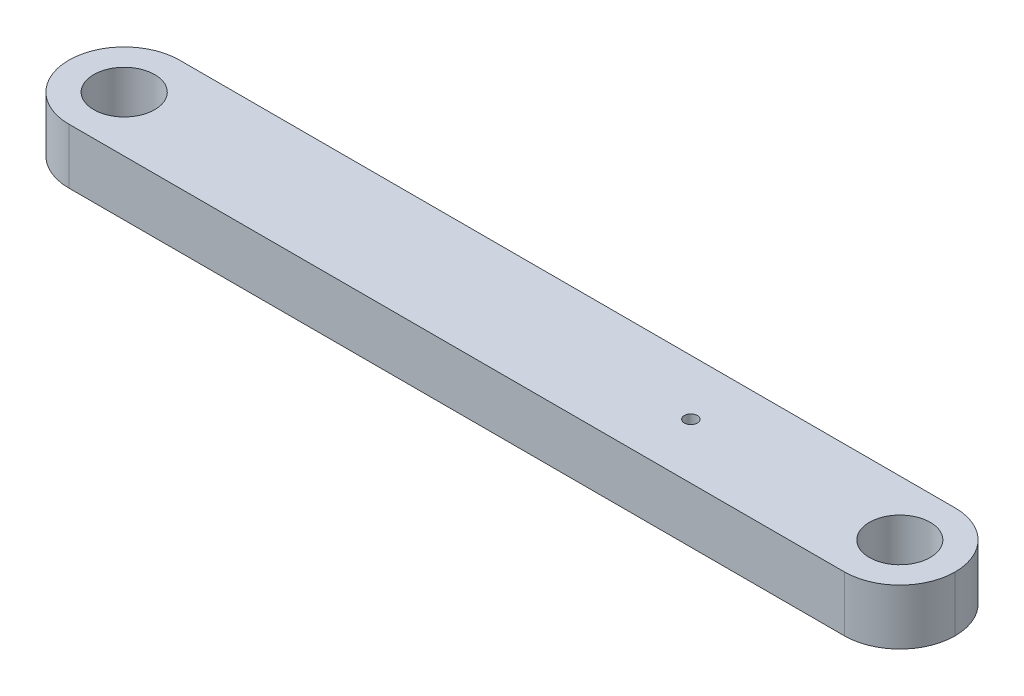
SolidWorks part; units mm, degrees
ref_plane "Front Plane" through (0, 0, 0) normal (0, 0, 1) x (1, 0, 0)
ref_plane "Top Plane" through (0, 0, 0) normal (0, 1, 0) x (1, 0, 0)
ref_plane "Right Plane" through (0, 0, 0) normal (1, 0, 0) x (0, 0, -1)
sketch "Sketch1" plane through (0, 0, 0) normal (0, 1, 0) x (1, 0, 0)
  line L0 (-44.45, 0) -> (0, 0) construction
  line L1 (-50.8, -6.35) -> (50.8, -6.35) construction
  line L2 (-50.8, -6.35) -> (-50.8, 6.35)
  line L3 (-50.8, 6.35) -> (50.8, 6.35)
  line L4 (50.8, -6.35) -> (50.8, 6.35)
  line L5 (-50.8, -6.35) -> (50.8, 6.35) construction
  line L6 (-50.8, 6.35) -> (50.8, -6.35) construction
  line L7 (0, 6.35) -> (0, -6.35) construction
  line L8 (-6.35, -31.75) -> (-6.35, 6.35) construction
  line L9 (-6.35, -31.75) -> (6.35, -31.75)
  line L10 (-6.35, 6.35) -> (6.35, 6.35)
  line L11 (6.35, -31.75) -> (6.35, 6.35) construction
  line L12 (-6.35, -31.75) -> (6.35, 6.35) construction
  line L13 (-6.35, 6.35) -> (6.35, -31.75) construction
  line L14 (-50.8, -6.35) -> (-6.35, -6.35)
  line L15 (-6.35, -6.35) -> (-6.35, -31.75)
  line L16 (6.35, -31.75) -> (6.35, -6.35)
  line L17 (6.35, -6.35) -> (50.8, -6.35)
  line L18 (-6.35, -6.35) -> (6.35, -6.35)
  circle A0 centre (-44.45, 0) radius 3.4925
  circle A1 centre (44.45, 0) radius 3.4925
  circle A2 centre (0, -25.4) radius 3.4925
  point P0 (0, 0)
  point P13 (0, -12.7)
  point P22 (0, -31.75)
  point P24 (0, 0)
  dimension "D5" = 12.7
  dimension "D6" = 38.1
  dimension "D3" = 6.35
  dimension "D4" = 6.985
  dimension "D7" = 6.35
  dimension "D1" = 101.6
  dimension "D2" = 12.7
extrude "Boss-Extrude1" add sketch "Sketch1" along normal blind 6.35 contours L16 L17 L4 L3 L2 L14 L15 L9 A2 A0 A1 region at (0, 0, 0)
fillet "Fillet1" radius 6.35 4 edges at (50.8, 3.175, -6.35) (-50.8, 3.175, -6.35) (-50.8, 3.175, 6.35) (50.8, 3.175, 6.35)
sketch "Sketch2" plane through (0, 6.35, 0) normal (0, 1, 0) x (1, 0, 0)
  line L0 (-20.5, 10.2) -> (10, 10.2) construction
  line L1 (20.5, -10.2) -> (-20.5, -10.2) construction
  line L2 (20.5, -10.2) -> (20.5, 10.2) construction
  line L3 (20.5, 10.2) -> (-20.5, 10.2) construction
  line L4 (-20.5, -10.2) -> (-20.5, 10.2) construction
  line L5 (20.5, -10.2) -> (-20.5, 10.2) construction
  line L6 (20.5, 10.2) -> (-20.5, -10.2) construction
  line L7 (10, 10.2) -> (10, -10.2) construction
  point P0 (0, 0)
  point P6 (0, 0)
  dimension "D1" = 41
  dimension "D2" = 20.4
  dimension "D3" = 30.5
sketch "Sketch3" plane through (0, 6.35, 0) normal (0, 1, 0) x (1, 0, 0)
  line L0 (20.5, -10.2) -> (20.5, 10.2) construction
  circle A0 centre (20.5, 0) radius 0.75
  dimension "D1" = 1.5
extrude "Cut-Extrude1" cut sketch "Sketch3" against normal through all
